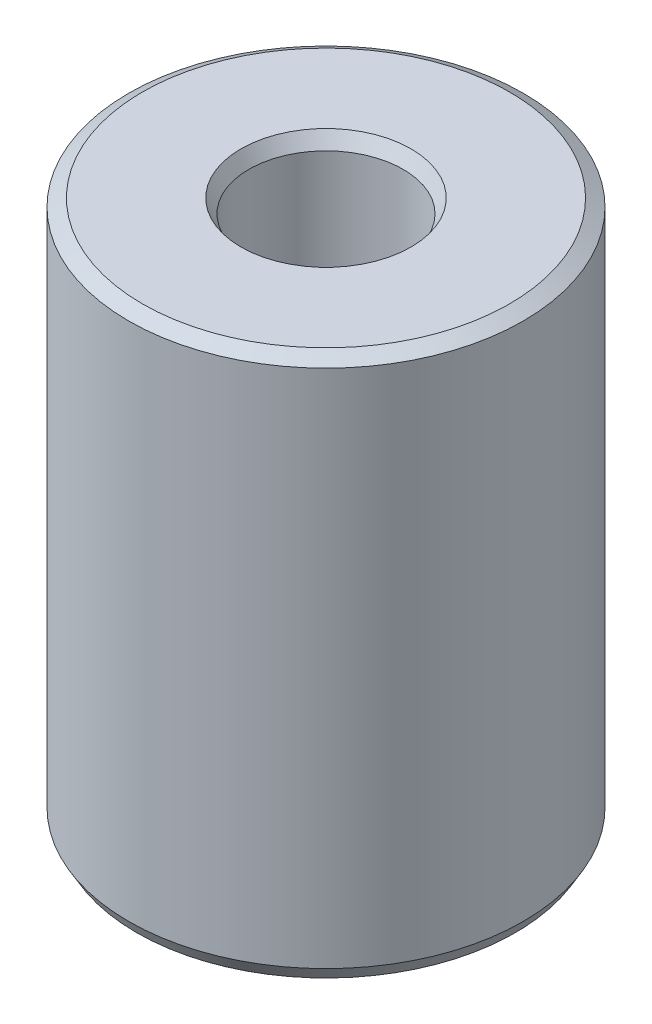
SolidWorks part; units mm, degrees
ref_plane "Front Plane" through (0, 0, 0) normal (0, 0, 1) x (1, 0, 0)
ref_plane "Top Plane" through (0, 0, 0) normal (0, 1, 0) x (1, 0, 0)
ref_plane "Right Plane" through (0, 0, 0) normal (1, 0, 0) x (0, 0, -1)
sketch "Sketch1" plane through (0, 0, 0) normal (0, 1, 0) x (1, 0, 0)
  circle A0 centre (0, 0) radius 15
  dimension "SLEEVE_OD" = 30
extrude "Boss-Extrude1" add sketch "Sketch1" along normal blind 41.1822
sketch "Sketch2" plane through (0, 0, 0) normal (0, 1, 0) x (1, 0, 0)
  circle A0 centre (0, 0) radius 5.8638
  dimension "BORE_D" = 11.7277
extrude "Cut-Extrude1" cut sketch "Sketch2" along normal through all
chamfer "Chamfer1" distance 0.6034 angle 60 4 edges at (0, 41.1822, 5.8638) (0, 0, 5.8638) (0, 0, 15) (0, 41.1822, 15) first distance on face at (0, 41.1822, 5.8638) first distance on face at (0, 0, 5.8638) first distance on face at (0, 41.1822, 15)
